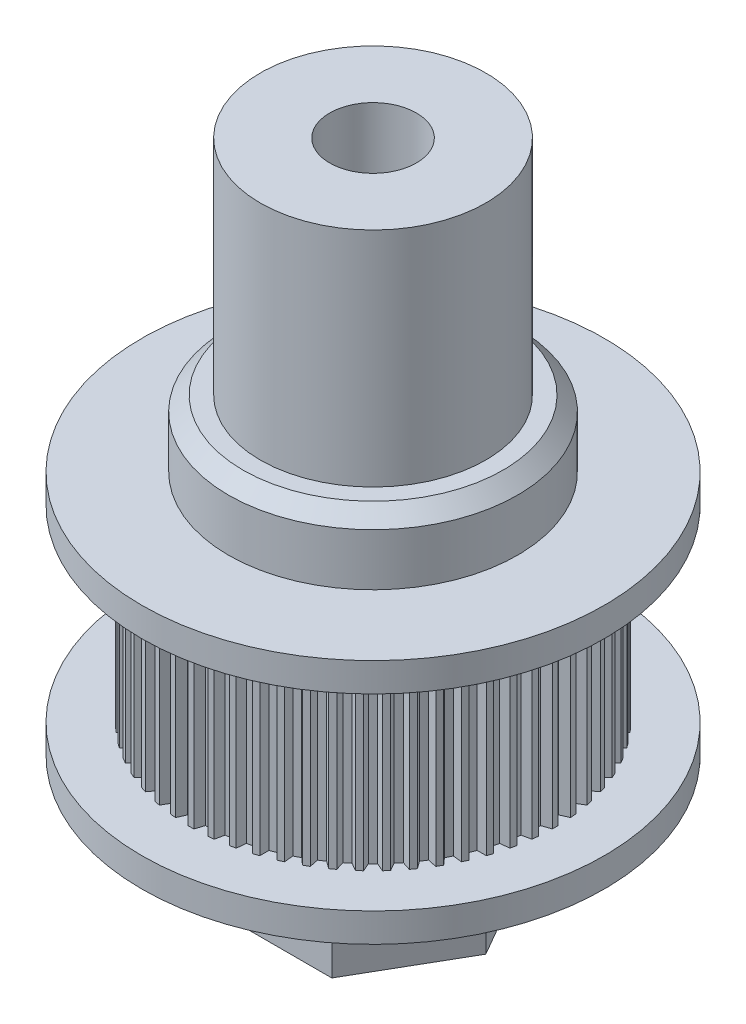
SolidWorks part; units mm, degrees
ref_plane "Front Plane" through (0, 0, 0) normal (0, 0, 1) x (1, 0, 0)
ref_plane "Top Plane" through (0, 0, 0) normal (0, 1, 0) x (1, 0, 0)
ref_plane "Right Plane" through (0, 0, 0) normal (1, 0, 0) x (0, 0, -1)
sketch "Sketch1" plane through (0, 0, 0) normal (0, 1, 0) x (1, 0, 0)
  line L1 (1.95, 3.3775) -> (-1.95, 3.3775)
  line L2 (-1.95, 3.3775) -> (-3.9, 0)
  line L3 (-3.9, 0) -> (-1.95, -3.3775)
  line L4 (-1.95, -3.3775) -> (1.95, -3.3775)
  line L5 (1.95, -3.3775) -> (3.9, 0)
  line L6 (3.9, 0) -> (1.95, 3.3775)
  circle A0 centre (0, 0) radius 3.9 construction
  circle A1 centre (0, 0) radius 3.3775 construction
  point P3 (0.353, 0.6114)
  point P11 (0, 0)
  dimension "D1" = 7.8
extrude "Boss-Extrude1" add sketch "Sketch1" along normal blind 4
sketch "Sketch2" plane through (0, 4, 0) normal (0, 1, 0) x (1, 0, 0)
  circle A0 centre (0, 0) radius 8
  circle A1 centre (0, 0) radius 5
  line M3 (3.9, 0) -> (1.95, 3.3775)
  line M4 (1.95, 3.3775) -> (-1.95, 3.3775)
  line M5 (-1.95, 3.3775) -> (-3.9, 0)
  line M6 (-3.9, 0) -> (-1.95, -3.3775)
  line M7 (-1.95, -3.3775) -> (1.95, -3.3775)
  line M8 (1.95, -3.3775) -> (3.9, 0)
  dimension "D1" = 16
  dimension "D2" = 10
extrude "Boss-Extrude2" add sketch "Sketch2" along normal blind 1 separate body contours A1 M3 M8 M7 M6 M5 M4 | M8 M3 M4 M5 M6 M7 | A0 A1 | A1 | A0 region at (-7.7737, 4, 0) region at (-4.8586, 4, 0) region at (0, 4, 0)
sketch "Sketch4" plane through (0, 5, 0) normal (0, 1, 0) x (1, 0, 0)
  circle A0 centre (0, 0) radius 6
  dimension "D1" = 12
extrude "Boss-Extrude3" add sketch "Sketch4" along normal blind 6.5
sketch "Sketch5" plane through (0, 11.5, 0) normal (0, 1, 0) x (1, 0, 0)
  line L0 (0, 0) -> (0, 6) construction
  line L1 (-0.2, 5.9967) -> (-0.1, 6.3)
  line L2 (-0.1, 6.3) -> (0.1, 6.3)
  line L3 (0.1, 6.3) -> (0.2, 5.9967)
  line L4 (0, 6.3) -> (0, 6) construction
  circle A1 centre (0, 0) radius 6
  arc A2 (0.2, 5.9967) -> (-0.2, 5.9967) centre (0, 0) ccw
  point P9 (0, 0)
  point P10 (0, 0)
  point P11 (0, 0)
  dimension "D2" = 0.3
  dimension "D3" = 0.2
  dimension "D4" = 0.2
  dimension "D5" = 0.2
  dimension "D1" = 0
extrude "Boss-Extrude4" add sketch "Sketch5" against normal up to surface (6.5 mm away) up to face at (0, 5, 6)
pattern_circular "CirPattern1" count 60 over 360 about axis through (0, 11.5, 0) along (0, -1, 0) of "Boss-Extrude4"
sketch "Sketch6" plane through (0, 11.5, 0) normal (0, 1, 0) x (1, 0, 0)
  circle A0 centre (0, 0) radius 8
  dimension "D1" = 16
extrude "Boss-Extrude5" add sketch "Sketch6" along normal blind 1
sketch "Sketch7" plane through (0, 12.5, 0) normal (0, 1, 0) x (1, 0, 0)
  circle A0 centre (0, 0) radius 3.9
  dimension "D1" = 7.8
extrude "Boss-Extrude6" add sketch "Sketch7" along normal blind 10
sketch "Sketch8" plane through (0, 0, 0) normal (0, -1, 0) x (1, 0, 0)
  circle A0 centre (0, 0) radius 1.5
  dimension "D1" = 3
extrude "Cut-Extrude1" cut sketch "Sketch8" against normal through all
sketch "Sketch9" plane through (0, 12.5, 0) normal (0, 1, 0) x (1, 0, 0)
  circle A0 centre (0, 0) radius 5
  circle A1 centre (0, 0) radius 1.5 construction
  circle A2 centre (0, 0) radius 1.5
  dimension "D1" = 10
extrude "Boss-Extrude7" add sketch "Sketch9" along normal blind 2.3
chamfer "Chamfer1" distance 0.5 angle 45 1 edges at (0, 14.8, 5)
